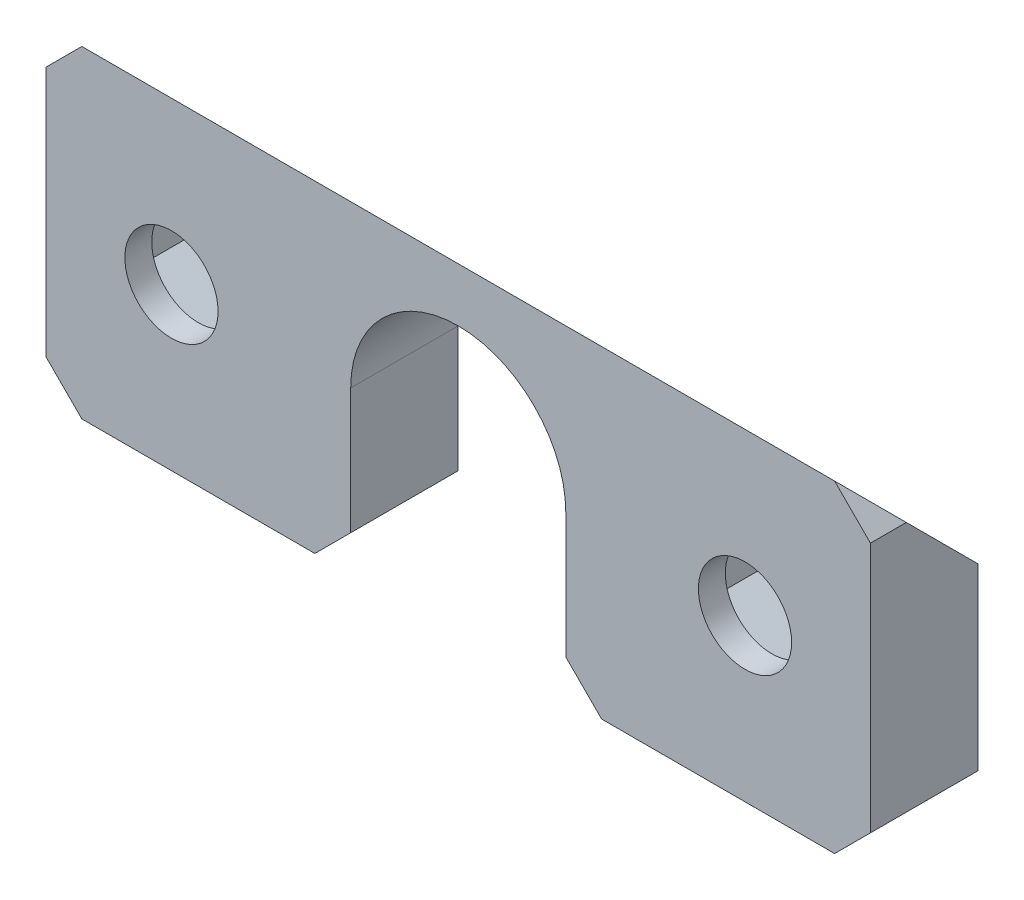
SolidWorks part; units mm, degrees
ref_plane "Front Plane" through (0, 0, 0) normal (0, 0, 1) x (1, 0, 0)
ref_plane "Top Plane" through (0, 0, 0) normal (0, 1, 0) x (1, 0, 0)
ref_plane "Right Plane" through (0, 0, 0) normal (1, 0, 0) x (0, 0, -1)
sketch "Sketch1" plane through (0, 0, 789.6201) normal (0, 0, -1) x (-1, 0, 0)
  line L2 (8.2108, -513.2989) -> (8.2108, -527.2989)
  line L3 (10.2108, -529.2989) -> (25.2108, -529.2989)
  line L4 (54.2108, -513.2989) -> (54.2108, -527.2989)
  line L9 (8.2108, -513.2989) -> (10.2108, -511.2989)
  line L10 (8.2108, -527.2989) -> (10.2108, -529.2989)
  line L11 (52.2108, -529.2989) -> (54.2108, -527.2989)
  line L12 (52.2108, -511.2989) -> (54.2108, -513.2989)
  line L13 (31.2108, -516.2989) -> (31.2108, -520.2989) construction
  line L14 (10.9608, -517.8452) -> (10.9608, -522.7527)
  line L15 (10.9608, -522.7527) -> (15.2108, -525.2064)
  line L16 (15.2108, -525.2064) -> (19.4608, -522.7527)
  line L17 (19.4608, -522.7527) -> (19.4608, -517.8452)
  line L18 (19.4608, -517.8452) -> (15.2108, -515.3915)
  line L19 (15.2108, -515.3915) -> (10.9608, -517.8452)
  line L21 (47.2108, -515.3915) -> (42.9608, -517.8452)
  line L22 (42.9608, -517.8452) -> (42.9608, -522.7527)
  line L23 (42.9608, -522.7527) -> (47.2108, -525.2064)
  line L24 (47.2108, -525.2064) -> (51.4608, -522.7527)
  line L25 (51.4608, -522.7527) -> (51.4608, -517.8452)
  line L26 (51.4608, -517.8452) -> (47.2108, -515.3915)
  line L27 (25.2108, -520.2989) -> (25.2108, -529.2989)
  line L28 (37.2108, -520.2989) -> (37.2108, -529.2989)
  line L29 (37.2108, -529.2989) -> (52.2108, -529.2989)
  line L30 (10.2108, -511.2989) -> (52.2108, -511.2989)
  circle A3 centre (15.2108, -520.2989) radius 4.25 construction
  arc A4 (33.0442, -523.8541) -> (29.3775, -523.8541) centre (31.2108, -520.2989) ccw construction
  circle A5 centre (47.2108, -520.2989) radius 4.25 construction
  arc A6 (37.2108, -520.2989) -> (25.2108, -520.2989) centre (31.2108, -520.2989) ccw
  point P3 (8.2108, -511.2989)
  point P4 (54.2108, -529.2989)
  point P5 (8.2108, -529.2989)
  point P6 (54.2108, -511.2989)
  dimension "D2" = 17
  dimension "D3" = 17
  dimension "D4" = 6
  dimension "D5" = 8.5
  dimension "D6" = 0
  dimension "D12" = 8.5
extrude "Boss-Extrude1" add sketch "Sketch1" along normal blind 6
sketch "Sketch2" plane through (0, 0, 789.6201) normal (0, 0, 1) x (1, 0, 0)
  line L0 (-54.2108, -513.2989) -> (-52.2108, -511.2989)
  line L1 (-52.2108, -511.2989) -> (-39.2108, -511.2989)
  line L2 (-54.2108, -513.2989) -> (-54.2108, -527.2989)
  line L3 (-52.2108, -529.2989) -> (-37.2108, -529.2989)
  line L4 (-8.1201, -513.2989) -> (-8.1201, -527.2989)
  line L5 (-54.2108, -527.2989) -> (-52.2108, -529.2989)
  line L6 (-10.1201, -529.2989) -> (-8.1201, -527.2989)
  line L7 (-10.1201, -511.2989) -> (-8.1201, -513.2989)
  line L8 (-39.2108, -511.2989) -> (-23.2108, -511.2989)
  line L9 (-37.2108, -520.2989) -> (-37.2108, -529.2989)
  line L10 (-23.2108, -511.2989) -> (-10.1201, -511.2989)
  line L11 (-25.2108, -520.2989) -> (-25.2108, -529.2989)
  line L12 (-25.2108, -529.2989) -> (-10.1201, -529.2989)
  circle A0 centre (-47.2108, -520.2989) radius 2.6
  circle A1 centre (-15.2108, -520.2989) radius 2.6
  arc A3 (-25.2108, -520.2989) -> (-37.2108, -520.2989) centre (-31.2108, -520.2989) ccw
  point P0 (-54.2108, -511.2989)
  point P1 (-8.1201, -529.2989)
  point P2 (-54.2108, -529.2989)
  point P3 (-8.1201, -511.2989)
  point P21 (-37.2108, -511.2989)
  point P23 (-25.2108, -511.2989)
  dimension "D1" = 5.2
  dimension "D2" = 5.2
  dimension "D14" = 2
  dimension "D15" = 2
extrude "Boss-Extrude2" add sketch "Sketch2" against normal blind 1.5
chamfer "Chamfer1" distance 2 angle 45 2 edges at (-25.2108, -529.2989, 786.6201) (-37.2108, -529.2989, 786.6201)
chamfer "Chamfer2" distance 6 angle 45 1 edges at (-31.2108, -511.2989, 783.6201)
